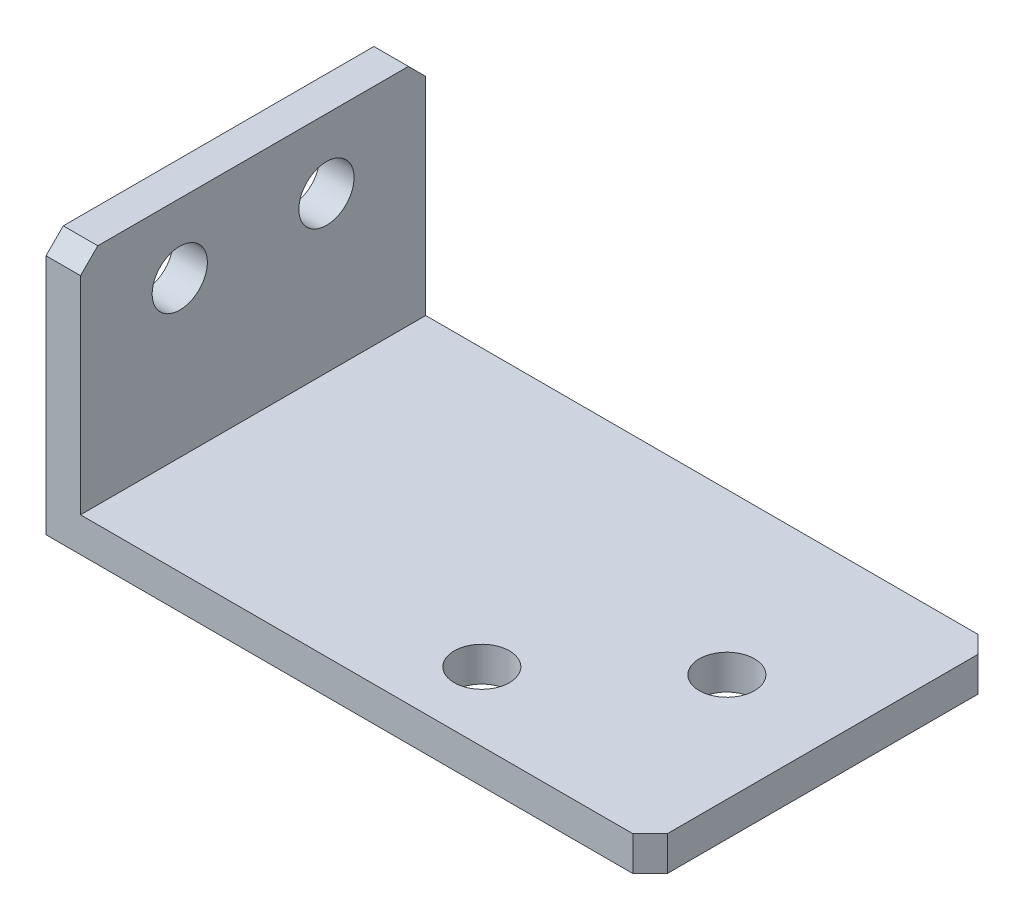
SolidWorks part; units mm, degrees
material "6063-T5"
ref_plane "Спереди" through (0, 0, 0) normal (0, 0, 1) x (1, 0, 0)
ref_plane "Сверху" through (0, 0, 0) normal (0, 1, 0) x (1, 0, 0)
ref_plane "Справа" through (0, 0, 0) normal (1, 0, 0) x (0, 0, -1)
sketch "Sketch1" plane through (0, 0, 0) normal (0, 0, 1) x (1, 0, 0)
  line L0 (0, 0) -> (35, 0)
  line L1 (35, 0) -> (35, 2)
  line L2 (35, 2) -> (2, 2)
  line L3 (2, 2) -> (2, 15)
  line L4 (2, 15) -> (0, 15)
  line L5 (0, 15) -> (0, 0)
  dimension "D1" = 35
  dimension "D2" = 15
  dimension "D4" = 2
extrude "Base" add sketch "Sketch1" along normal blind 20
chamfer "Chamfer1" distance 1 angle 45 4 edges at (35, 1, 0) (1, 15, 0) (1, 15, 20) (35, 1, 20)
hole_wizard "Ø3.2 (3.2) MountSide" positions "Sketch6" profile "Sketch7" hole size "Ø3.2" standard "ANSI Metric" end condition through all
sketch "Sketch6" plane through (0, 0, 0) normal (-1, 0, 0) x (0, 0, 1)
  line L1 (20, 0) -> (0, 0) construction
  line L3 (10, 0) -> (10, 2.8485) construction
  point P0 (5.75, 11)
  point P2 (14.25, 11)
  dimension "D1" = 8.5
  dimension "D3" = 11
sketch "Sketch7" plane through (0, 11, 5.75) normal (0, 1, 0) x (0, 0, 1)
  line L0 (0, 0) -> (0, 35)
  line L1 (0, 35) -> (1.6, 35)
  line L2 (1.6, 35) -> (1.6, 0)
  line L5 (1.6, 0) -> (0, 0)
  line L11 (0, -6.35) -> (0, 107.95) construction
  dimension "Thru Hole Dia." = 3.2
  dimension "Thru Hole Depth" = 35
hole_wizard "Ø3.2 (3.2) CableChainSide" positions "Sketch8" profile "Sketch9" hole size "Ø3.2" standard "ANSI Metric" end condition through all
sketch "Sketch8" plane through (0, 0, 0) normal (0, -1, 0) x (-1, 0, 0)
  line L0 (0, -20) -> (-34, -20) construction
  line L1 (0, -20) -> (0, 0) construction
  point P0 (-28.75, -9.3)
  point P2 (-21.25, -16)
  dimension "D1" = 7.5
  dimension "D2" = 6.7
  dimension "D3" = 4
  dimension "D4" = 21.25
sketch "Sketch9" plane through (28.75, 0, 9.3) normal (1, 0, 0) x (0, 0, -1)
  line L0 (0, 0) -> (0, 15)
  line L1 (0, 15) -> (1.6, 15)
  line L2 (1.6, 15) -> (1.6, 0)
  line L5 (1.6, 0) -> (0, 0)
  line L11 (0, -6.35) -> (0, 107.95) construction
  dimension "Thru Hole Dia." = 3.2
  dimension "Thru Hole Depth" = 15
